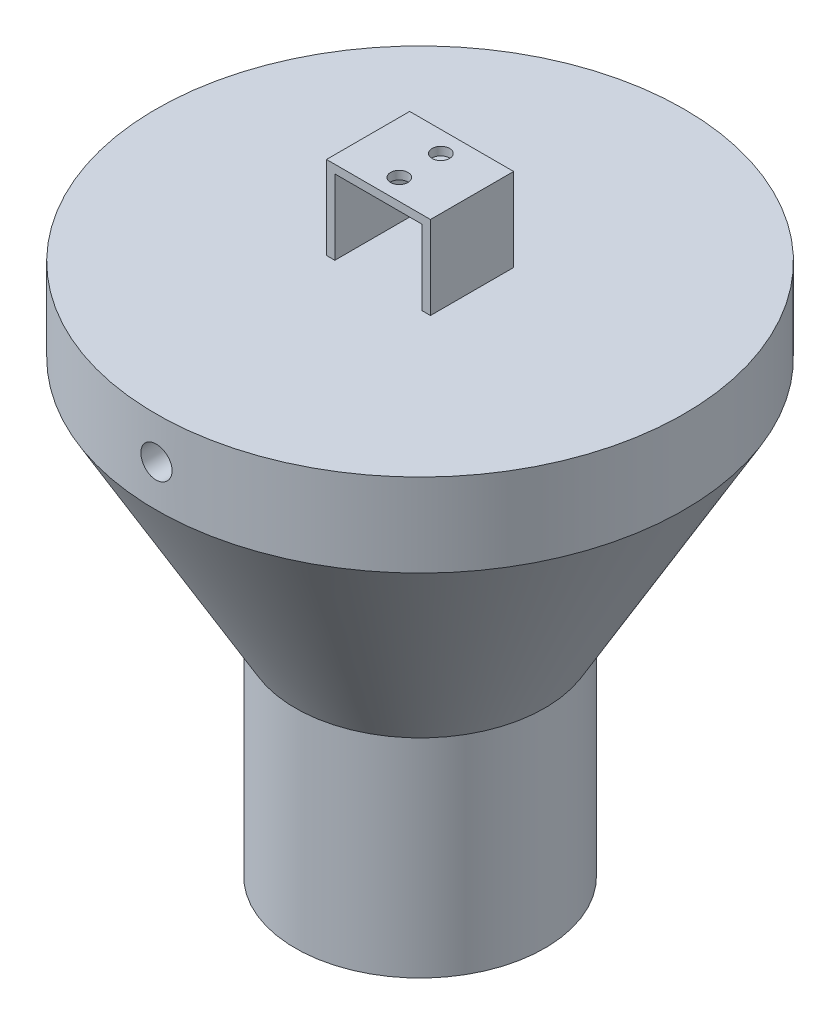
SolidWorks part; units mm, degrees
ref_plane "Front Plane" through (0, 0, 0) normal (0, 0, 1) x (1, 0, 0)
ref_plane "Top Plane" through (0, 0, 0) normal (0, 1, 0) x (1, 0, 0)
ref_plane "Right Plane" through (0, 0, 0) normal (1, 0, 0) x (0, 0, -1)
sketch "Sketch1" plane through (0, 0, 0) normal (0, 0, 1) x (1, 0, 0)
  line L0 (0, 0) -> (0, 88)
  line L1 (0, 0) -> (-30, 0)
  line L2 (-30, 0) -> (-30, 50)
  line L3 (-30, 50) -> (-63.4863, 108)
  line L5 (-63.4863, 108) -> (-63.4863, 128)
  line L6 (-63.4863, 128) -> (0, 128)
  line L7 (0, 128) -> (0, 88)
  line L8 (-30, 50) -> (0, 50)
  dimension "D1" = 88
  dimension "D2" = 30
  dimension "D3" = 50
  dimension "D4" = 150
  dimension "D5" = 20
  dimension "D6" = 63.4863
revolve "Revolve1" add sketch "Sketch1" angle 360 about L0 region at (-26.7225, 93.7976, 0)
shell "Shell1" thickness 10 removed face at (0, 50, -30)
sketch "Sketch4" plane through (0, 0, 0) normal (0, 0, 1) x (1, 0, 0)
  line L0 (0, 128) -> (0, 108) construction
  line L1 (63.4863, 128) -> (-63.4863, 128) construction
  line L2 (63.4863, 108) -> (-63.4863, 108) construction
  circle A0 centre (0, 118) radius 3.75
  dimension "D1" = 7.5
extrude "Cut-Extrude2" cut sketch "Sketch4" against normal mid plane 150
revolve "Revolve2" add sketch "Sketch1<3>" angle 360 about L0 region at (-15, 25, 0)
sketch "Sketch1<3>" plane through (0, 0, 0) normal (0, 0, 1) x (1, 0, 0) same geometry as "Sketch1"
shell "Shell3" thickness 12 removed face at (0, 0, -30) removed face at (0, 50, 18.453)
sketch "Sketch5" plane through (0, 0, 0) normal (0, -1, 0) x (1, 0, 0)
  circle A0 centre (0, 0) radius 20.5
  circle A1 centre (0, 0) radius 25
  dimension "D1" = 41
  dimension "D2" = 50
extrude "Cut-Extrude3" cut sketch "Sketch5" against normal blind 2.5
sketch "Sketch7" plane through (0, 0, 0) normal (0, 0, 1) x (1, 0, 0)
  line L0 (0, 128) -> (0, 143) construction
  line L1 (63.4863, 128) -> (-63.4863, 128) construction
  line L2 (7.5, 128) -> (10.5, 128)
  line L3 (-7.5, 128) -> (7.5, 128) construction
  line L4 (-7.5, 128) -> (-7.5, 143) construction
  line L5 (-7.5, 143) -> (7.5, 143) construction
  line L6 (7.5, 128) -> (7.5, 143) construction
  line L7 (-7.5, 128) -> (7.5, 143) construction
  line L8 (-7.5, 143) -> (7.5, 128) construction
  line L9 (10.5, 128) -> (10.5, 146)
  line L10 (10.5, 146) -> (-10.5, 146)
  line L11 (-10.5, 128) -> (-10.5, 146)
  line L12 (10.5, 128) -> (12.5, 128)
  line L13 (12.5, 128) -> (12.5, 148)
  line L14 (12.5, 148) -> (-12.5, 148)
  line L15 (-12.5, 128) -> (-12.5, 148)
  line L16 (-10.5, 128) -> (-12.5, 128)
  point P5 (0, 135.5)
  point P15 (0, 146)
  point P20 (0, 148)
  dimension "D1" = 15
  dimension "D2" = 15
  dimension "D3" = 3
  dimension "D4" = 3
  dimension "D5" = 2
  dimension "D6" = 2
extrude "Boss-Extrude1" add sketch "Sketch7" along normal mid plane 20 contours L16 L11 L10 L9 L12 L13 L14 L15 region at (10.8202, 137, 0)
sketch "Sketch8" plane through (0, 148, 0) normal (0, 1, 0) x (1, 0, 0)
  line L0 (0, 10) -> (0, 0) construction
  line L1 (12.5, 10) -> (-12.5, 10) construction
  line L2 (0, 0) -> (0, -10) construction
  line L3 (-12.5, 0) -> (12.5, 0) construction
  line L4 (-12.5, -10) -> (-12.5, 10) construction
  line L5 (12.5, -10) -> (12.5, 10) construction
  line L6 (12.5, -10) -> (-12.5, -10) construction
  circle A0 centre (0, 5) radius 2.1
  circle A1 centre (0, -5) radius 2.1
  dimension "D1" = 4.2
extrude "Cut-Extrude4" cut sketch "Sketch8" against normal blind 10
